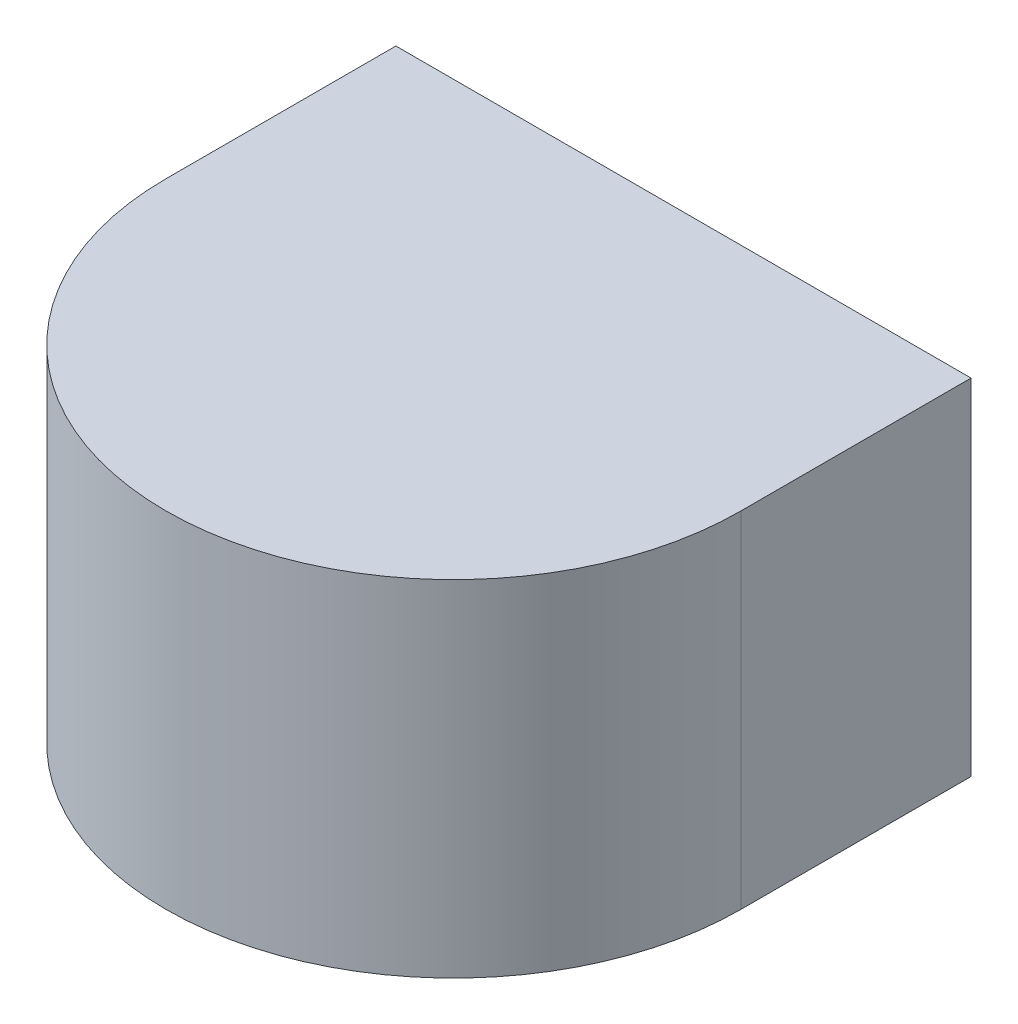
SolidWorks part; units mm, degrees
ref_plane "Front Plane" through (0, 0, 0) normal (0, 0, 1) x (1, 0, 0)
ref_plane "Top Plane" through (0, 0, 0) normal (0, 1, 0) x (1, 0, 0)
ref_plane "Right Plane" through (0, 0, 0) normal (1, 0, 0) x (0, 0, -1)
sketch "Sketch3" plane through (0, 0, 0) normal (0, 1, 0) x (1, 0, 0)
  line L0 (-125, 0) -> (125, 0) construction
  line L1 (0, 0) -> (0, 70) construction
  line L2 (-125, 0) -> (-125, 100)
  line L3 (-125, 100) -> (-100, 100)
  line L4 (-100, 100) -> (-100, 70)
  line L5 (-100, 70) -> (100, 70)
  line L6 (100, 100) -> (100, 70)
  line L7 (125, 100) -> (100, 100)
  line L8 (125, 0) -> (125, 100)
  arc A0 (125, 0) -> (-125, 0) centre (0, 0) cw
  point P3 (0, 0)
  point P14 (0, 70)
  dimension "D1" = 250
  dimension "D2" = 100
  dimension "D3" = 30
  dimension "D4" = 200
extrude "Boss-Extrude1" add sketch "Sketch3" along normal blind 100
sketch "Sketch4" plane through (0, 100, 0) normal (0, 1, 0) x (1, 0, 0)
  line L0 (-100, 100) -> (100, 100)
  line L7 (125, 0) -> (125, 100)
  line L8 (125, 100) -> (100, 100)
  line L9 (100, 100) -> (100, 70)
  line L10 (100, 70) -> (-100, 70)
  line L11 (-100, 70) -> (-100, 100)
  line L12 (-100, 100) -> (-125, 100)
  line L13 (-125, 100) -> (-125, 0)
  line L14 (125, 0) -> (125, 100)
  line L15 (125, 100) -> (100, 100)
  line L19 (-100, 100) -> (-125, 100)
  line L20 (-125, 100) -> (-125, 0)
  arc A1 (-125, 0) -> (125, 0) centre (0, 0) ccw
  arc A2 (-125, 0) -> (125, 0) centre (0, 0) ccw
  dimension "D1" = 0
extrude "Boss-Extrude2" add sketch "Sketch4" along normal blind 50
